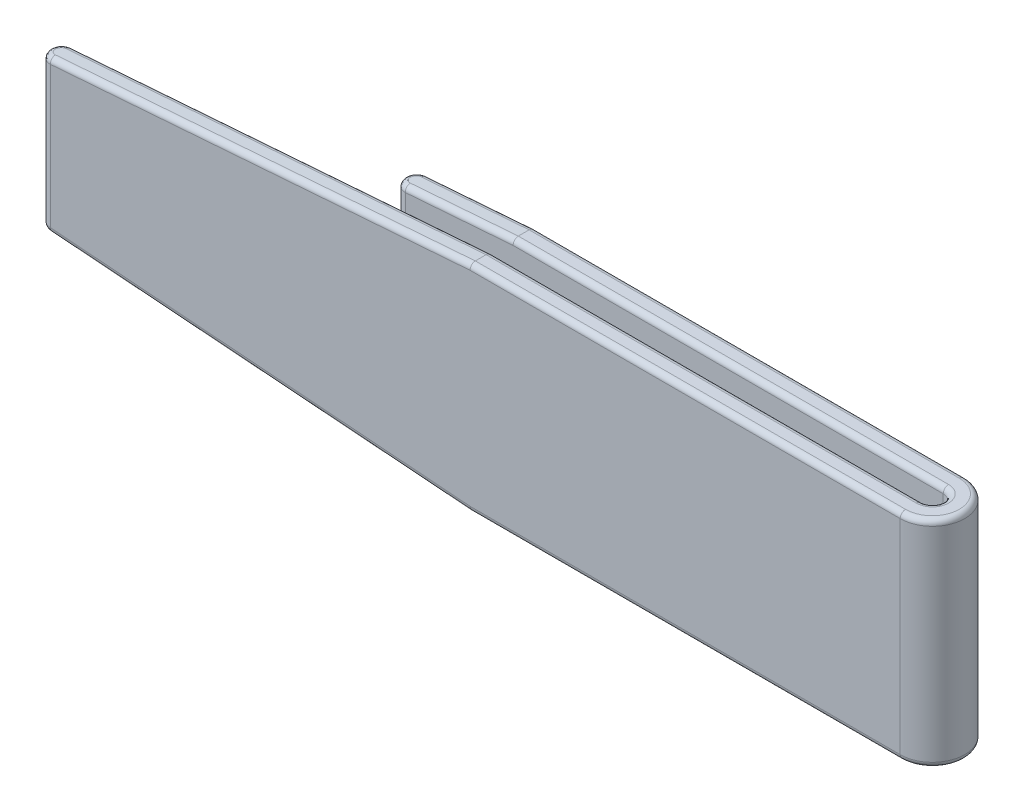
SolidWorks part; units mm, degrees
ref_plane "Front Plane" through (0, 0, 0) normal (0, 0, 1) x (1, 0, 0)
ref_plane "Top Plane" through (0, 0, 0) normal (0, 1, 0) x (1, 0, 0)
ref_plane "Right Plane" through (0, 0, 0) normal (1, 0, 0) x (0, 0, -1)
sketch "Sketch1" plane through (0, 0, 0) normal (0, 1, 0) x (1, 0, 0)
  line L1 (0, 0) -> (80, 0)
  line L2 (0, 2) -> (80, 2)
  line L3 (80, 6) -> (30, 6)
  line L4 (30, 4) -> (80, 4)
  arc A0 (0, 0) -> (0, 2) centre (0, 1) cw
  arc A1 (80, 0) -> (80, 6) centre (80, 3) ccw
  arc A3 (30, 6) -> (30, 4) centre (30, 5) ccw
  arc A4 (80, 2) -> (80, 4) centre (80, 3) ccw
  dimension "D2" = 1
  dimension "D3" = 3
  dimension "D1" = 2
  dimension "D4" = 80
  dimension "D5" = 50
extrude "Boss-Extrude1" add sketch "Sketch1" along normal blind 20
sketch "Sketch6" plane through (0, 0, 0) normal (0, 0, 1) x (1, 0, 0)
  line L0 (40, 20) -> (0, 17)
  line L1 (0, 20) -> (80, 20) construction
  line L2 (0, 17) -> (0, 3)
  line L3 (0, 3) -> (40, 0)
  line L4 (0, 0) -> (80, 0) construction
  line L5 (40, 0) -> (-0.8619, 0)
  line L6 (-0.8619, 0) -> (-0.8619, 20)
  line L7 (-0.8619, 20) -> (40, 20)
  dimension "D1" = 3
  dimension "D2" = 3
extrude "Cut-Extrude4" cut sketch "Sketch6" against normal blind 20
fillet "Fillet1" 2 edges at (0, 10, -2) (0, 10, 0) type full round first side face at (40, 10, -2) second side face at (40, 10, 0) middle face at (0, 10, -1)
fillet "Fillet3" radius 0.5 12 edges at (29, 19.175, -5) (60, 20, -4) (81, 20, -3) (60, 20, -6) (83, 20, -3) (0, 17, -1) (35, 19.625, -6) (35, 19.625, -4) (60, 20, -2) (60, 20, 0) (20.5, 18.5375, -2) (20.5, 18.5375, 0)
fillet "Fillet4" radius 0.5 12 edges at (0, 3, -1) (60, 0, -4) (29, 0.825, -5) (20.5, 1.4625, 0) (20.5, 1.4625, -2) (83, 0, -3) (81, 0, -3) (60, 0, 0) (60, 0, -2) (35, 0.375, -6) (35, 0.375, -4) (60, 0, -6)
sketch "Sketch7" plane through (0, 0, -2) normal (0, 0, -1) x (-1, 0, 0)
  line L1 (0, 11.4922) -> (4.4994, 11.4922)
  line L2 (0, 11.4922) -> (0, -2.4175)
  line L3 (0, -2.4175) -> (4.4994, -2.4175)
  line L4 (4.4994, 11.4922) -> (4.4994, -2.4175)
extrude "Cut-Extrude5" cut sketch "Sketch7" against normal blind 10
sketch "Sketch8" plane through (0, 0, 0) normal (0, 0, 1) x (1, 0, 0)
  line L1 (-0.6438, 11.2032) -> (-2.2641, 11.2032)
  line L2 (-0.6438, 11.2032) -> (-0.6438, 22.1274)
  line L3 (-0.6438, 22.1274) -> (-2.2641, 22.1274)
  line L4 (-2.2641, 11.2032) -> (-2.2641, 22.1274)
extrude "Cut-Extrude6" cut sketch "Sketch8" against normal blind 10
